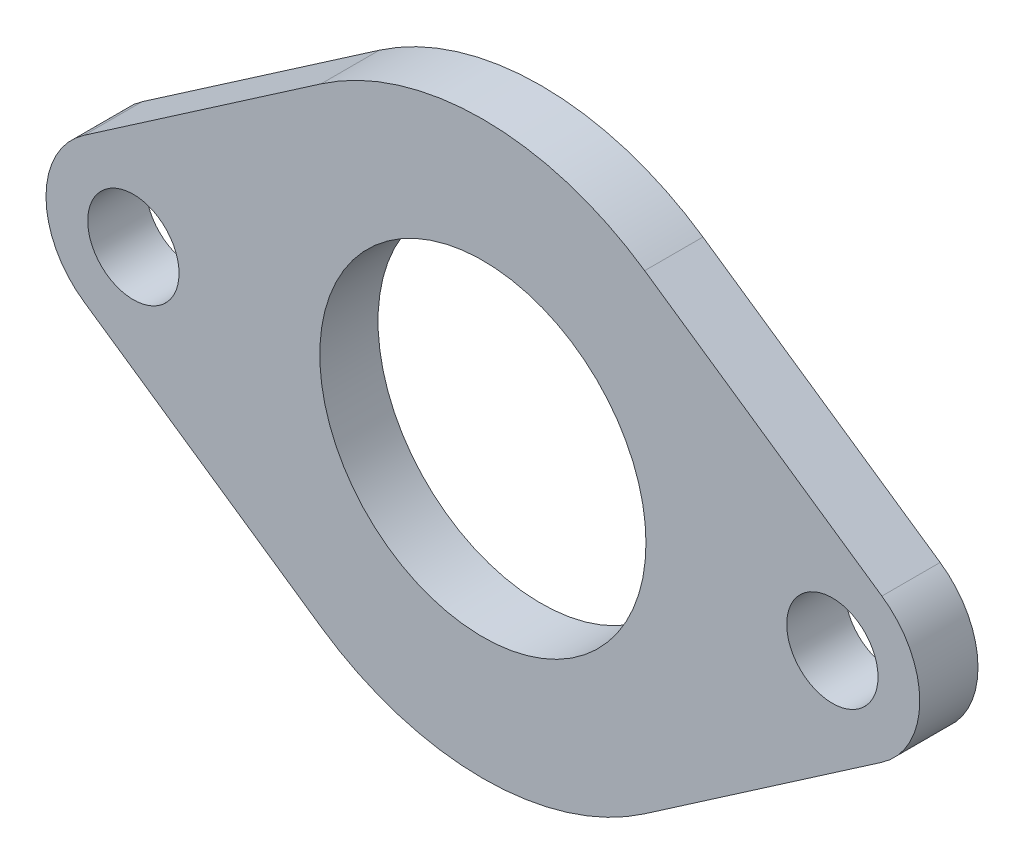
SolidWorks part; units mm, degrees
material "PET"
ref_plane "Front Plane" through (0, 0, 0) normal (0, 0, 1) x (1, 0, 0)
ref_plane "Top Plane" through (0, 0, 0) normal (0, 1, 0) x (1, 0, 0)
ref_plane "Right Plane" through (0, 0, 0) normal (1, 0, 0) x (0, 0, -1)
sketch "Sketch1" plane through (0, 0, 0) normal (0, 0, 1) x (1, 0, 0)
  line L0 (-21.7494, 3.9236) -> (-8.8194, 12.8192)
  line L1 (-21.7494, -3.9236) -> (-8.8194, -12.8192)
  line L2 (8.8194, -12.8192) -> (21.7494, -3.9236)
  line L3 (21.7494, 3.9236) -> (8.8194, 12.8192)
  arc A0 (-8.8194, -12.8192) -> (8.8194, -12.8192) centre (0, 0) ccw
  circle A1 centre (-19.05, 0) radius 2.4892
  circle A2 centre (19.05, 0) radius 2.4892
  circle A3 centre (0, 0) radius 8.89
  arc A4 (-15.2844, -2.9158) -> (-15.2844, 2.9158) centre (-19.05, 0) ccw construction
  arc A5 (21.7494, -3.9236) -> (21.7494, 3.9236) centre (19.05, 0) ccw
  arc A6 (-15.2844, -2.9158) -> (-8.8194, -12.8192) centre (0, 0) ccw construction
  arc A7 (-21.7494, -3.9236) -> (-15.2844, -2.9158) centre (-19.05, 0) ccw construction
  arc A8 (-15.2844, 2.9158) -> (-15.2844, -2.9158) centre (0, 0) ccw construction
  arc A9 (-15.2844, 2.9158) -> (-21.7494, 3.9236) centre (-19.05, 0) ccw construction
  arc A10 (-21.7494, 3.9236) -> (-21.7494, -3.9236) centre (-19.05, 0) ccw
  arc A11 (-8.8194, 12.8192) -> (-15.2844, 2.9158) centre (0, 0) ccw construction
  arc A12 (8.8194, -12.8192) -> (15.2844, -2.9158) centre (0, 0) ccw construction
  arc A13 (8.8194, 12.8192) -> (-8.8194, 12.8192) centre (0, 0) ccw
  arc A14 (15.2844, -2.9158) -> (21.7494, -3.9236) centre (19.05, 0) ccw construction
  arc A15 (15.2844, 2.9158) -> (15.2844, -2.9158) centre (19.05, 0) ccw construction
  arc A16 (15.2844, -2.9158) -> (15.2844, 2.9158) centre (0, 0) ccw construction
  arc A17 (21.7494, 3.9236) -> (15.2844, 2.9158) centre (19.05, 0) ccw construction
  arc A18 (15.2844, 2.9158) -> (8.8194, 12.8192) centre (0, 0) ccw construction
  dimension "D1" = 31.1201
  dimension "D2" = 19.05
  dimension "D3" = 19.05
  dimension "D4" = 4.9784
  dimension "D5" = 17.78
  dimension "D6" = 9.525
extrude "Boss-Extrude1" add sketch "Sketch1" along normal blind 3.175
